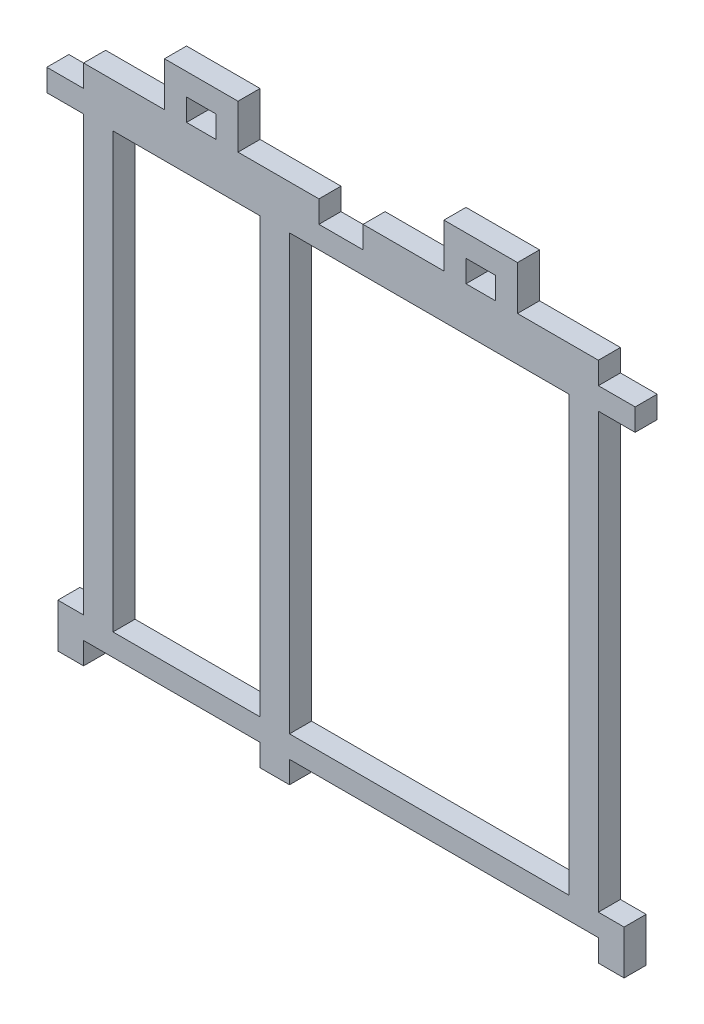
SolidWorks part; units mm, degrees
material "Custom Plastic"
ref_plane "Front Plane" through (0, 0, 0) normal (0, 0, 1) x (1, 0, 0)
ref_plane "Top Plane" through (0, 0, 0) normal (0, 1, 0) x (1, 0, 0)
ref_plane "Right Plane" through (0, 0, 0) normal (1, 0, 0) x (0, 0, -1)
sketch "Sketch1" plane through (0, 0, 0) normal (0, 0, 1) x (1, 0, 0)
  line L75 (5, -3) -> (0, -3)
  line L76 (0, -3) -> (0, 0)
  line L77 (0, 0) -> (5, 0)
  line L78 (5, 0) -> (5, 3)
  line L79 (5, 3) -> (37, 3)
  line L80 (37, 3) -> (37, 0)
  line L81 (37, 0) -> (43, 0)
  line L82 (43, 0) -> (43, 3)
  line L83 (43, 3) -> (75, 3)
  line L84 (75, 3) -> (75, 0)
  line L85 (75, 0) -> (80, 0)
  line L86 (80, 0) -> (80, -3)
  line L87 (80, -3) -> (75, -3)
  line L88 (75, -3) -> (75, -62)
  line L89 (75, -62) -> (78.5, -62)
  line L90 (78.5, -62) -> (78.5, -68)
  line L91 (78.5, -68) -> (75, -68)
  line L92 (75, -68) -> (75, -65)
  line L93 (75, -65) -> (33, -65)
  line L94 (33, -65) -> (33, -68)
  line L95 (33, -68) -> (29, -68)
  line L96 (29, -68) -> (29, -65)
  line L97 (29, -65) -> (5, -65)
  line L98 (5, -65) -> (5, -68)
  line L99 (5, -68) -> (1.5, -68)
  line L100 (1.5, -68) -> (1.5, -62)
  line L101 (1.5, -62) -> (5, -62)
  line L102 (5, -3) -> (5, -62)
  line L103 (9, -62) -> (29, -62)
  line L104 (29, -62) -> (29, -3)
  line L105 (29, -3) -> (9, -3)
  line L106 (9, -3) -> (9, -62)
  line L107 (33, -3) -> (33, -62)
  line L108 (33, -62) -> (71, -62)
  line L109 (71, -62) -> (71, -3)
  line L110 (71, -3) -> (33, -3)
  point P56 (76.75, -62)
  dimension "D4" = 59
  dimension "D13" = 6
  dimension "D14" = 3
  dimension "D15" = 3
  dimension "D16" = 32
  dimension "D17" = 32
  dimension "D18" = 5
  dimension "D19" = 5
  dimension "D20" = 59
  dimension "D21" = 6
  dimension "D22" = 3.5
  dimension "D23" = 3
  dimension "D24" = 42
  dimension "D25" = 4
  dimension "D26" = 24
  dimension "D27" = 3.5
  dimension "D28" = 6
  dimension "D29" = 4
  dimension "D30" = 4
  dimension "D31" = 20
extrude "Boss-Extrude1" add sketch "Sketch1" along normal blind 3
sketch "Sketch2" plane through (0, 0, 3) normal (0, 0, 1) x (1, 0, 0)
  line L0 (37, 3) -> (5, 3) construction
  line L1 (16, 3) -> (26, 3)
  line L2 (16, 3) -> (16, 9)
  line L3 (16, 9) -> (26, 9)
  line L4 (26, 3) -> (26, 9)
  line L5 (5, 3) -> (5, 0) construction
  line L6 (19, 3) -> (23, 3)
  line L7 (19, 3) -> (19, 6)
  line L8 (19, 6) -> (23, 6)
  line L9 (23, 3) -> (23, 6)
  line L10 (40, 0) -> (40, 10.82) construction
  line L11 (43, 0) -> (37, 0) construction
  line L12 (57, 3) -> (57, 6)
  line L13 (61, 6) -> (57, 6)
  line L14 (61, 3) -> (61, 6)
  line L15 (61, 3) -> (57, 3)
  line L16 (54, 3) -> (54, 9)
  line L17 (64, 9) -> (54, 9)
  line L18 (64, 3) -> (64, 9)
  line L19 (64, 3) -> (54, 3)
  line M28 (75, 3) -> (43, 3)
  line M32 (37, 3) -> (5, 3)
  dimension "D1" = 10
  dimension "D2" = 3
  dimension "D3" = 3
  dimension "D4" = 3
  dimension "D5" = 3
  dimension "D6" = 11
extrude "Boss-Extrude2" add sketch "Sketch2" against normal blind 3 contours L9 L4 L3 L2 L7 L8 M32 | L18 L17 L16 L12 L13 L14 M28 region at (21, 6.375, 3) region at (59, 6.375, 3)
